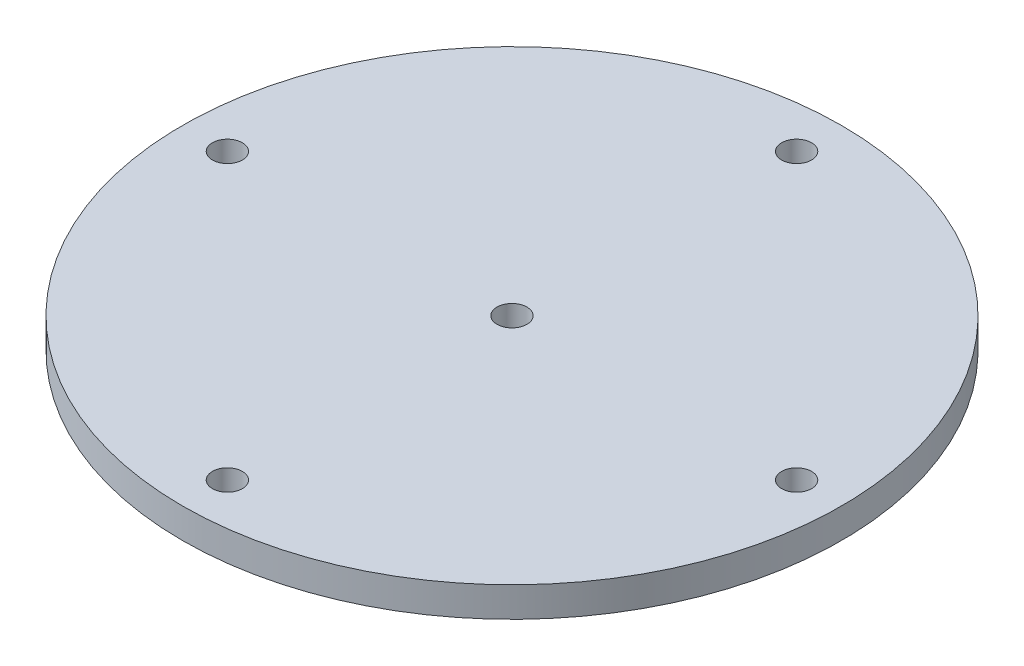
SolidWorks part; units mm, degrees
ref_plane "Front Plane" through (0, 0, 0) normal (0, 0, 1) x (1, 0, 0)
ref_plane "Top Plane" through (0, 0, 0) normal (0, 1, 0) x (1, 0, 0)
ref_plane "Right Plane" through (0, 0, 0) normal (1, 0, 0) x (0, 0, -1)
sketch "Sketch1" plane through (0, 0, 0) normal (0, 1, 0) x (1, 0, 0)
  circle A0 centre (0, 0) radius 220
  circle A1 centre (0, 190) radius 10
  circle A2 centre (0, 0) radius 190 construction
  circle A3 centre (190, 0) radius 10
  circle A4 centre (0, -190) radius 10
  circle A5 centre (-190, 0) radius 10
  circle A6 centre (0, 0) radius 10
  point P15 (0, 0)
  dimension "D1" = 440
  dimension "D2" = 380
  dimension "D3" = 20
  dimension "D4" = 4
extrude "Boss-Extrude1" add sketch "Sketch1" along normal blind 20
sketch "Sketch2" plane through (0, 0, 0) normal (0, 0, 1) x (1, 0, 0)
  line L0 (0, 0) -> (0, -10)
  line L1 (0, -10) -> (10, 0)
  line L2 (-220, 0) -> (220, 0) construction
  line L3 (0, 0) -> (10, 0)
  line L4 (-180, 0) -> (-190, -10)
  line L5 (190, 0) -> (190, -10)
  line L6 (-190, 0) -> (-190, -10)
  line L7 (-190, 0) -> (-180, 0)
  line L8 (190, 0) -> (180, 0)
  line L9 (180, 0) -> (190, -10)
  point P9 (-190.3001, -0.9324)
  point P12 (-201.5995, -10)
  point P13 (-189.349, -0.8911)
  dimension "D1" = 10
  dimension "D2" = 10
revolve "Revolve2" add sketch "Sketch2" angle 360 about L0 region at (3.3333, -3.3333, 0)
revolve "Revolve3" add sketch "Sketch2<3>" angle 360 about L6 region at (-186.6667, -3.3333, 0)
sketch "Sketch2<3>" plane through (0, 0, 0) normal (0, 0, 1) x (1, 0, 0) same geometry as "Sketch2"
sketch "Sketch4" plane through (0, 0, 0) normal (1, 0, 0) x (0, 0, -1)
  line L0 (-180, 0) -> (-190, -10)
  line L1 (-190, -10) -> (-190, 0)
  line L2 (-190, 0) -> (-180, 0)
  line L3 (0, 0) -> (0, -10) construction
  line L4 (190, -10) -> (190, 0)
  line L5 (180, 0) -> (190, -10)
  line L6 (190, 0) -> (180, 0)
  dimension "D1" = 10
  dimension "D2" = 10
revolve "Revolve4" add sketch "Sketch4" angle 360 about L1 region at (0, -3.3333, 186.6667)
revolve "Revolve5" add sketch "Sketch2<4>" angle 360 about L5 region at (186.6667, -3.3333, 0)
sketch "Sketch2<4>" plane through (0, 0, 0) normal (0, 0, 1) x (1, 0, 0) same geometry as "Sketch2"
revolve "Revolve7" add sketch "Sketch4<3>" angle 360 about L4 region at (0, -3.3333, -186.6667)
sketch "Sketch4<3>" plane through (0, 0, 0) normal (1, 0, 0) x (0, 0, -1) same geometry as "Sketch4"
